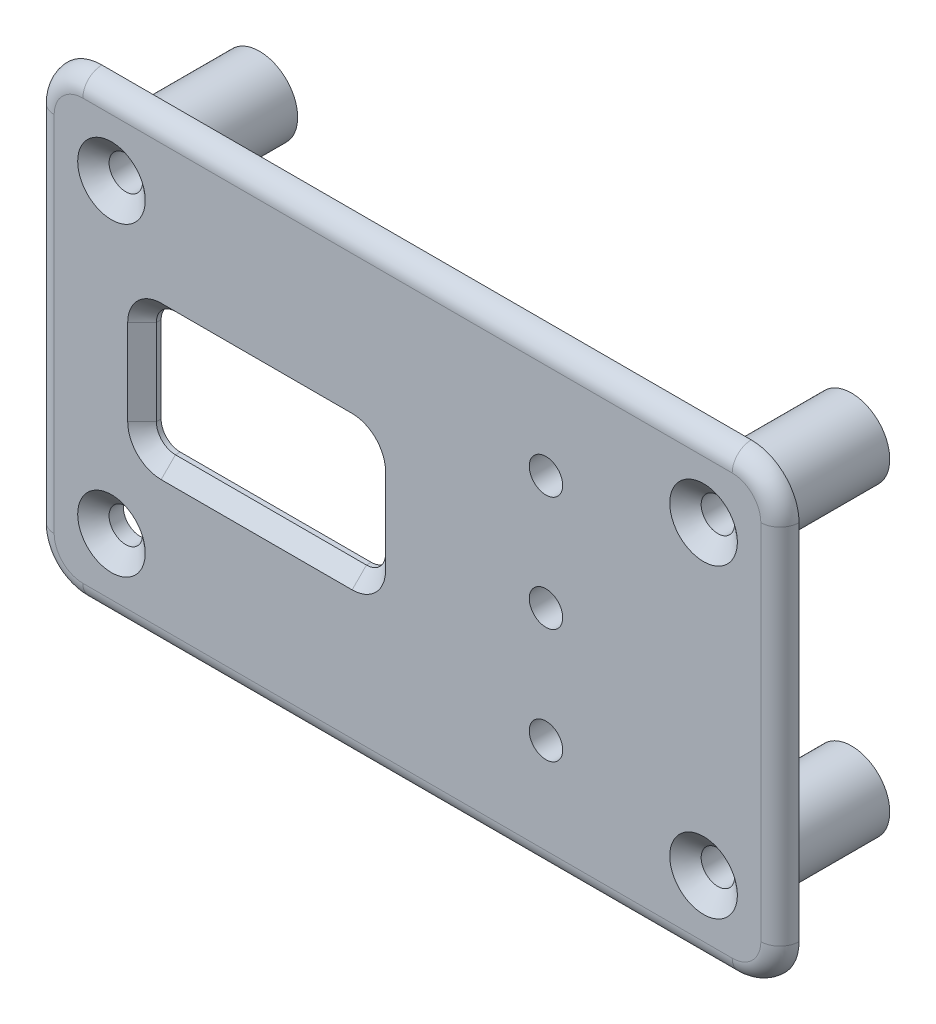
SolidWorks part; units mm, degrees
ref_plane "Piano frontale" through (0, 0, 0) normal (0, 0, 1) x (1, 0, 0)
ref_plane "Piano superiore" through (0, 0, 0) normal (0, 1, 0) x (1, 0, 0)
ref_plane "Piano destro" through (0, 0, 0) normal (1, 0, 0) x (0, 0, -1)
sketch "Schizzo1" plane through (0, 0, 0) normal (0, 0, 1) x (1, 0, 0)
  line L0 (-33, 22) -> (33, 22) construction
  line L1 (-34, -24) -> (34, -24)
  line L2 (-39, -19) -> (-39, 19)
  line L3 (-34, 24) -> (34, 24)
  line L4 (39, -19) -> (39, 19)
  line L5 (-39, -24) -> (39, 24) construction
  line L6 (-39, 24) -> (39, -24) construction
  line L7 (37, -18) -> (37, 18) construction
  line L8 (-33, -22) -> (33, -22) construction
  line L9 (-37, -18) -> (-37, 18) construction
  line L10 (-39, -24) -> (39, -24) construction
  line L11 (-39, -24) -> (-39, 24) construction
  line L12 (39, -24) -> (39, 24) construction
  line L13 (-39, 24) -> (39, 24) construction
  line L14 (-37, -22) -> (37, -22) construction
  line L15 (-37, -22) -> (-37, 22) construction
  line L16 (37, -22) -> (37, 22) construction
  line L17 (-37, 22) -> (37, 22) construction
  arc A0 (-34, -24) -> (-39, -19) centre (-34, -19) cw
  arc A1 (34, -24) -> (39, -19) centre (34, -19) ccw
  arc A2 (34, 24) -> (39, 19) centre (34, 19) cw
  arc A3 (-39, 19) -> (-34, 24) centre (-34, 19) cw
  arc A4 (-33, -22) -> (-37, -18) centre (-33, -18) cw construction
  arc A5 (37, -18) -> (33, -22) centre (33, -18) cw construction
  arc A6 (33, 22) -> (37, 18) centre (33, 18) cw construction
  arc A7 (-33, 22) -> (-37, 18) centre (-33, 18) ccw construction
  point P0 (0, 0)
  dimension "D4" = 5
  dimension "D5" = 4
  dimension "D1" = 78
  dimension "D2" = 48
  dimension "D3" = 2
extrude "Estrusione-Estrusione1" add sketch "Schizzo1" along normal blind 2
sketch "Schizzo2" plane through (0, 0, 0) normal (0, 0, -1) x (-1, 0, 0)
  line L0 (-37, -18) -> (-37, 18) construction
  line L1 (33, -22) -> (-33, -22) construction
  line L2 (37, -18) -> (37, 18) construction
  line L3 (33, 22) -> (-33, 22) construction
  line L4 (-37, -18) -> (-37, 18) construction
  line L5 (33, -22) -> (-33, -22) construction
  line L6 (37, -18) -> (37, 18) construction
  line L7 (33, 22) -> (-33, 22) construction
  line L8 (-36.5, -18) -> (-36.5, 18)
  line L9 (33, 21.5) -> (-33, 21.5)
  line L10 (36.5, -18) -> (36.5, 18)
  line L11 (33, -21.5) -> (-33, -21.5)
  arc A0 (-37, -18) -> (-33, -22) centre (-33, -18) ccw construction
  arc A1 (-33, 22) -> (-37, 18) centre (-33, 18) ccw construction
  arc A2 (33, -22) -> (37, -18) centre (33, -18) ccw construction
  arc A3 (37, 18) -> (33, 22) centre (33, 18) ccw construction
  arc A4 (-37, -18) -> (-33, -22) centre (-33, -18) ccw construction
  arc A5 (-33, 22) -> (-37, 18) centre (-33, 18) ccw construction
  arc A6 (33, -22) -> (37, -18) centre (33, -18) ccw construction
  arc A7 (37, 18) -> (33, 22) centre (33, 18) ccw construction
  arc A8 (-33, 21.5) -> (-36.5, 18) centre (-33, 18) ccw
  arc A9 (36.5, 18) -> (33, 21.5) centre (33, 18) ccw
  arc A10 (33, -21.5) -> (36.5, -18) centre (33, -18) ccw
  arc A11 (-36.5, -18) -> (-33, -21.5) centre (-33, -18) ccw
  dimension "D1" = 0.5
extrude "Estrusione-Estrusione2" add sketch "Schizzo2" along normal blind 1
sketch "Schizzo3" plane through (0, 0, -1) normal (0, 0, -1) x (-1, 0, 0)
  circle A3 centre (-31, 16) radius 1.75
  circle A4 centre (-31, 16) radius 4
  circle A5 centre (-31, -16) radius 1.75
  circle A6 centre (-31, -16) radius 4
  circle A7 centre (31, -16) radius 1.75 construction
  circle A8 centre (31, -16) radius 4 construction
  circle A9 centre (31, 16) radius 4
  circle A10 centre (31, 16) radius 1.75
  dimension "D1" = 8
  dimension "D2" = 3.5
extrude "Estrusione-Estrusione3" add sketch "Schizzo3" along normal blind 12.5
sketch "Schizzo4" plane through (0, 0, -1) normal (0, 0, -1) x (-1, 0, 0)
  line L0 (-36.5, 0) -> (36.5, 0) construction
  line L1 (-36.5, 18) -> (-36.5, -18) construction
  line L2 (36.5, -18) -> (36.5, 18) construction
  circle A0 centre (-31, -16) radius 1.75 construction
  circle A1 centre (-31, 16) radius 1.75 construction
  circle A2 centre (31, 16) radius 1.75 construction
  circle A4 centre (-31, -16) radius 1.75
  circle A5 centre (-31, 16) radius 1.75
  circle A6 centre (31, 16) radius 1.75
  circle A8 centre (31, -16) radius 1.75
extrude "Taglio-Estrusione1" cut sketch "Schizzo4" against normal blind 13
sketch "Schizzo5" plane through (0, 0, -1) normal (0, 0, -1) x (-1, 0, 0)
  line L0 (3.8, 6) -> (27.8, 6)
  line L1 (4.8, 5) -> (26.8, 5) construction
  line L2 (4.8, 5) -> (4.8, -6) construction
  line L3 (4.8, -6) -> (26.8, -6) construction
  line L4 (26.8, 5) -> (26.8, -6) construction
  line L5 (27.8, 6) -> (27.8, -7)
  line L6 (3.8, -7) -> (27.8, -7)
  line L7 (3.8, 6) -> (3.8, -7)
  dimension "D1" = 1
extrude "Taglio-Estrusione2" cut sketch "Schizzo5" against normal blind 13
sketch "Schizzo6" plane through (0, 0, -1) normal (0, 0, -1) x (-1, 0, 0)
  line L20 (27.8, -7) -> (3.8, 6) construction
  line L21 (33.3, 11) -> (-1.7, 11)
  line L22 (33.3, 11) -> (33.3, -12)
  line L23 (33.3, -12) -> (-1.7, -12)
  line L24 (-1.7, 11) -> (-1.7, -12)
  line L25 (33.3, 11) -> (-1.7, -12) construction
  line L26 (33.3, -12) -> (-1.7, 11) construction
  line L27 (27.8, -7) -> (27.8, 6) construction
  line L28 (3.8, -7) -> (27.8, -7) construction
  point P2 (0, 0)
  point P3 (15.8, -0.5)
  point P4 (26.8, -6)
  point P5 (27.8, -7)
  point P10 (0, 0)
  point P11 (3.8, 6)
  point P50 (15.8, -0.5)
  dimension "D1" = 23
  dimension "D2" = 35
extrude "Taglio-Estrusione3" cut sketch "Schizzo6" against normal blind 1
fillet "Raccordo1" radius 2 8 edges at (-37.5355, 22.5355, 2) (0, 24, 2) (37.5355, 22.5355, 2) (39, 0, 2) (37.5355, -22.5355, 2) (0, -24, 2) (-37.5355, -22.5355, 2) (-39, 0, 2)
fillet "Raccordo2" radius 2 4 edges at (-27.8, -7, 1) (-3.8, -7, 1) (-3.8, 6, 1) (-27.8, 6, 1)
chamfer "Smusso1" distance 1.5 angle 45 8 edges at (-3.8, -0.5, 2) (-4.3858, -6.4142, 2) (-4.3858, 5.4142, 2) (-15.8, -7, 2) (-15.8, 6, 2) (-27.2142, -6.4142, 2) (-27.2142, 5.4142, 2) (-27.8, -0.5, 2)
chamfer "Smusso2" distance 1.5 angle 50 4 edges at (29.25, 16, 2) (29.25, -16, 2) (-32.75, -16, 2) (-32.75, 16, 2) first distance on face at (29.25, 16, -13.5) first distance on face at (29.25, -16, -13.5) first distance on face at (-29.25, -16, -1) first distance on face at (-32.75, 16, -13.5)
sketch "Schizzo7" plane through (0, 0, -1) normal (0, 0, -1) x (-1, 0, 0)
  circle A0 centre (-14.5, 12) radius 1.75
  circle A1 centre (-14.5, 0) radius 1.75
  circle A2 centre (-14.5, -12) radius 1.75
  circle A3 centre (-14.5, 12) radius 3.25
  circle A4 centre (-14.5, 0) radius 3.25
  circle A5 centre (-14.5, -12) radius 3.25
  dimension "D1" = 3.5
  dimension "D2" = 1.5
extrude "Estrusione-Estrusione4" add sketch "Schizzo7" along normal blind 7
sketch "Schizzo8" plane through (0, 0, -1) normal (0, 0, -1) x (-1, 0, 0)
  circle A0 centre (-14.5, 12) radius 1.75
  circle A1 centre (-14.5, 0) radius 1.75
  circle A2 centre (-14.5, -12) radius 1.75
  dimension "D1" = 3.5
extrude "Taglio-Estrusione4" cut sketch "Schizzo8" against normal blind 10
equation "\"D1@Estrusione-Estrusione3\"= 13.5-1"
